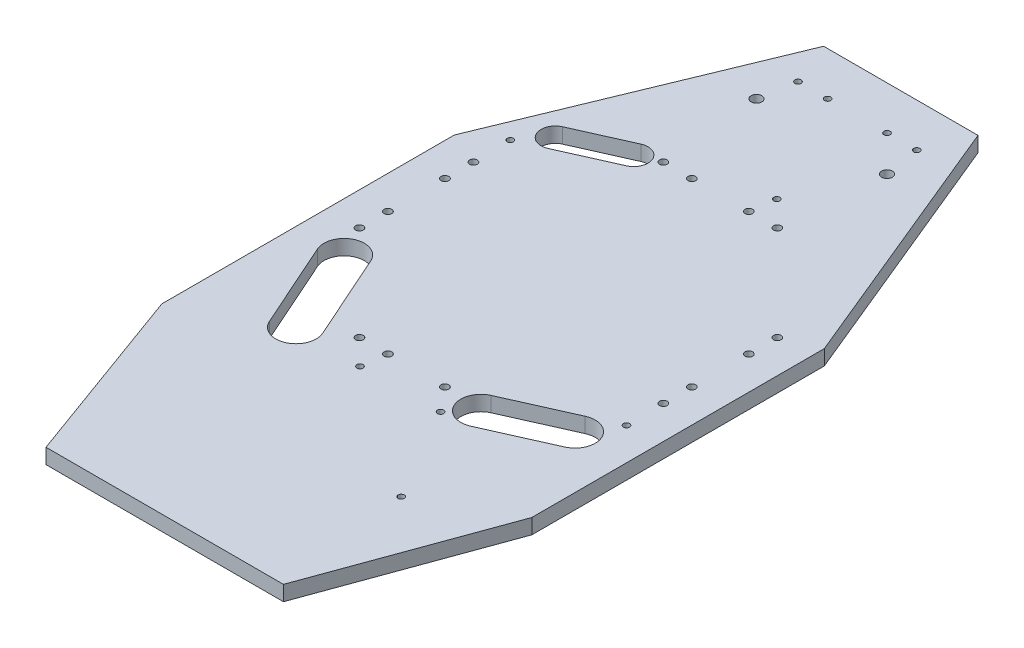
SolidWorks part; units mm, degrees
material "Pin"
ref_plane "Plan de face" through (0, 0, 0) normal (0, 0, 1) x (1, 0, 0)
ref_plane "Plan de dessus" through (0, 0, 0) normal (0, 1, 0) x (1, 0, 0)
ref_plane "Plan de droite" through (0, 0, 0) normal (1, 0, 0) x (0, 0, -1)
sketch "Esquisse3" plane through (0, 0, 0) normal (0, 1, 0) x (1, 0, 0)
  line L0 (-32.5, 140) -> (32.5, 140)
  line L1 (-77.9068, 29.8751) -> (-77.9068, -93.3266)
  line L2 (-77.9068, -93.3266) -> (-50, -170)
  line L3 (-50, -170) -> (50, -170)
  line L5 (77.9068, -93.3266) -> (77.9068, 29.8751)
  line L6 (50, -170) -> (77.9068, -93.3266)
  line L7 (-32.5, 140) -> (-77.9068, 29.8751)
  line L8 (32.5, 140) -> (77.9068, 29.8751)
  point P2 (0, 140)
  point P7 (0, -170)
  dimension "D1" = 170
  dimension "D2" = 140
  dimension "D3" = 65
  dimension "D4" = 70
  dimension "D5" = 100
sketch "TB_boltPattern" plane through (0, 0, 0) normal (0, 1, 0) x (1, 0, 0)
  line L0 (0, 143.3581) -> (0, -141.7362) construction
  line L1 (-23, 57.7) -> (-13, 57.7) construction
  line L2 (-23, 57.7) -> (-23, 43.7) construction
  line L3 (-23, 43.7) -> (-13, 43.7) construction
  line L4 (-13, 57.7) -> (-13, 43.7) construction
  line L5 (-57.7, 23) -> (-43.7, 23) construction
  line L6 (-57.7, 23) -> (-57.7, 13) construction
  line L7 (-57.7, 13) -> (-43.7, 13) construction
  line L8 (-43.7, 23) -> (-43.7, 13) construction
  line L9 (-204.4729, 0) -> (279.6048, 0) construction
  circle A0 centre (-24, 64) radius 1.6 construction
  circle A1 centre (-12, 64) radius 1.6 construction
  circle A2 centre (-64, 24) radius 1.6 construction
  circle A3 centre (-64, 12) radius 1.6 construction
  point P8 (-18, 57.7)
  dimension "D5" = 3.2
  dimension "D10" = 6.3
  dimension "D1" = 12
  dimension "D2" = 12
  dimension "D3" = 40
  dimension "D4" = 40
  dimension "D6" = 14
  dimension "D7" = 10
  dimension "D8" = 1
  dimension "D9" = 6.3
  dimension "D11" = 1
  dimension "D12" = 12
  dimension "D13" = 12
sketch "HB_Footprint" plane through (0, 0, 0) normal (0, 1, 0) x (1, 0, 0)
  line L0 (13.3793, 74.3875) -> (64.2603, -39.7884) construction
  line L1 (64.2603, -39.7884) -> (-13.3793, -74.3875) construction
  line L2 (13.3793, 74.3875) -> (-64.2603, 39.7884) construction
  line L3 (-64.2603, 39.7884) -> (-13.3793, -74.3875) construction
  line L8 (29.8751, 77.9068) -> (-77.9068, 29.8751) construction
  line L9 (-77.9068, 29.8751) -> (-29.8751, -77.9068) construction
  line L10 (-29.8751, -77.9068) -> (77.9068, -29.8751) construction
  line L11 (29.8751, 77.9068) -> (77.9068, -29.8751) construction
  line L12 (53.891, 24.0158) -> (-53.891, -24.0158) construction
  line L13 (-25.4405, 57.0879) -> (0, 0) construction
  circle A0 centre (13.3793, 74.3875) radius 1.6 construction
  circle A1 centre (64.2603, -39.7884) radius 1.6 construction
  circle A2 centre (-64.2603, 39.7884) radius 1.6 construction
  circle A3 centre (-13.3793, -74.3875) radius 1.6 construction
  point P10 (-53.891, -24.0158)
  point P19 (38.8198, 17.2996)
  dimension "D4" = 3.2
  dimension "D1" = 125
  dimension "D2" = 85
  dimension "D3" = 118
extrude "Plate" add sketch "Esquisse3" against normal blind 6.35
ref_axis "Axe1" through (0, 0, 0) along (0, 1, 0)
hole_wizard "Dégagement M32" positions "Esquisse9" profile "Esquisse10" hole size "M3" standard "Ansi Metric"
sketch "Esquisse9" plane through (0, 0, 0) normal (0, 1, 0) x (1, 0, 0)
  point P0 (-24, 64)
  point P3 (-12, 64)
  point P6 (-64, 24)
  point P9 (-64, 12)
sketch "Esquisse10" plane through (-24, 0, -64) normal (1, 0, 0) x (0, 0, 1)
  line L0 (0, 0) -> (0, 7.3114)
  line L1 (0, 7.3114) -> (1.6, 6.35)
  line L2 (1.6, 6.35) -> (1.6, 0)
  line L5 (1.6, 0) -> (0, 0)
  line L10 (0, 7.3114) -> (-1.6, 6.35) construction
  line L11 (0, -6.35) -> (0, 107.95) construction
  dimension "Diamètre du perçage" = 3.2
  dimension "Profondeur du perçage" = 6.35
  dimension "Angle de pointe" = 118
pattern_circular "Répétition circulaire2" count 4 over 360 about axis through (0, 0, 0) along (0, 1, 0) of "Dégagement M32"
hole_wizard "Dégagement M33" positions "Esquisse11" profile "Esquisse12" hole size "M3" standard "Ansi Metric"
sketch "Esquisse11" plane through (0, 0, 0) normal (0, 1, 0) x (1, 0, 0)
  point P0 (13.3793, 74.3875)
  point P3 (-64.2603, 39.7884)
  point P6 (-13.3793, -74.3875)
  point P9 (64.2603, -39.7884)
sketch "Esquisse12" plane through (13.3793, 0, -74.3875) normal (1, 0, 0) x (0, 0, 1)
  line L0 (0, 0) -> (0, 7.1311)
  line L1 (0, 7.1311) -> (1.3, 6.35)
  line L2 (1.3, 6.35) -> (1.3, 0)
  line L5 (1.3, 0) -> (0, 0)
  line L10 (0, 7.1311) -> (-1.3, 6.35) construction
  line L11 (0, -6.35) -> (0, 107.95) construction
  dimension "Diamètre du perçage" = 2.6
  dimension "Profondeur du perçage" = 6.35
  dimension "Angle de pointe" = 118
sketch "RegFootprint" plane through (0, 0, 0) normal (0, 1, 0) x (1, 0, 0)
  line L0 (27.48, 106.69) -> (-27.48, 106.69) construction
  line L2 (0, 79) -> (0, 106.69) construction
  line L3 (0, 200143.3581) -> (0, -200141.7362) construction
  line L4 (32.355, 79) -> (-32.355, 79) construction
  line L5 (32.355, 79) -> (32.355, 138.35) construction
  line L6 (32.355, 138.35) -> (-32.355, 138.35) construction
  line L7 (-32.355, 79) -> (-32.355, 138.35) construction
  line L8 (32.5, 140) -> (-32.5, 140) construction
  circle A0 centre (27.48, 106.69) radius 4.7701 construction
  circle A1 centre (-27.48, 106.69) radius 4.7701 construction
  circle A2 centre (12, 64) radius 1.6 construction
  point P4 (-31.5067, 170.618)
  point P8 (-85.837, 208.5527)
  point P9 (49.7222, 117.5736)
  point P13 (0, 0)
  point P14 (0, 79)
  point P17 (32.4415, 165.5032)
  point P20 (32.7199, 142.7624)
  dimension "D1" = 54.96
  dimension "D2" = 27.69
  dimension "D3" = 64.71
  dimension "D4" = 59.35
  dimension "D5" = 15
hole_wizard "Dégagement M51" positions "Esquisse16" profile "Esquisse17" hole size "M5" standard "Ansi Metric"
sketch "Esquisse16" plane through (0, 0, 0) normal (0, 1, 0) x (1, 0, 0)
  point P0 (27.48, 106.69)
  point P3 (-27.48, 106.69)
sketch "Esquisse17" plane through (27.48, 0, -106.69) normal (1, 0, 0) x (0, 0, 1)
  line L0 (0, 0) -> (0, 7.714)
  line L1 (0, 7.714) -> (2.27, 6.35)
  line L2 (2.27, 6.35) -> (2.27, 0)
  line L5 (2.27, 0) -> (0, 0)
  line L10 (0, 7.714) -> (-2.27, 6.35) construction
  line L11 (0, -6.35) -> (0, 107.95) construction
  dimension "Diamètre du perçage" = 4.54
  dimension "Profondeur du perçage" = 6.35
  dimension "Angle de pointe" = 118
sketch "puckFootprint" plane through (0, 0, 0) normal (0, 1, 0) x (1, 0, 0)
  line L0 (42.8335, -113.2396) -> (20.1785, -74) construction
  line L1 (-29.8568, -164.7163) -> (-60.7468, -111.2133) construction
  line L2 (31.506, -93.6198) -> (-45.3018, -137.9648) construction
  line L4 (31.506, -93.6198) -> (44.4964, -86.1198) construction
  line L7 (0, 200143.3581) -> (0, -200141.7362) construction
  circle A1 centre (20.1785, -74) radius 1.5 construction
  circle A2 centre (42.8335, -113.2396) radius 1.5 construction
  circle A3 centre (-60.7468, -111.2133) radius 1.5 construction
  circle A4 centre (-29.8568, -164.7163) radius 1.5 construction
  circle A5 centre (24, -64) radius 1.6 construction
  point P8 (0, -111.8098)
  point P11 (-25.6517, -126.6198)
  point P12 (0, 0)
  point P16 (74.8755, -425.5387)
  point P17 (70.056, -355.2747)
  point P19 (0, 0)
  point P20 (-37.2769, -223.5735)
  point P21 (-33.1557, -252.1317)
  point P22 (0, 0)
  point P23 (75.9498, -415.6514)
  point P26 (0, 0)
  point P27 (0, -102.3699)
  dimension "D4" = 3
  dimension "D9" = 10
  dimension "D1" = 36.38
  dimension "D2" = 45.31
  dimension "D3" = 52.31
  dimension "D5" = 61.78
  dimension "D6" = 15
  dimension "D7" = 60
  dimension "D8" = 81
hole_wizard "BoltPatternPuck" positions "Esquisse3D1" profile "Esquisse18" hole size "M3" standard "Ansi Metric"
sketch3d "Esquisse3D1"
  point P2 (20.1785, 0, 74)
  point P5 (42.8335, 0, 113.2396)
sketch "Esquisse18" plane through (20.1785, 0, 74) normal (1, 0, 0) x (0, 0, 1)
  line L0 (0, 0) -> (0, 7.1311)
  line L1 (0, 7.1311) -> (1.3, 6.35)
  line L2 (1.3, 6.35) -> (1.3, 0)
  line L5 (1.3, 0) -> (0, 0)
  line L10 (0, 7.1311) -> (-1.3, 6.35) construction
  line L11 (0, -6.35) -> (0, 107.95) construction
  dimension "Diamètre du perçage" = 2.6
  dimension "Profondeur du perçage" = 6.35
  dimension "Angle de pointe" = 118
sketch "Esquisse19" plane through (0, 0, 0) normal (0, 1, 0) x (1, 0, 0)
  line L0 (28.2989, -65.1199) -> (55.7011, -52.9085) construction
  line L1 (24.839, -57.356) -> (52.2412, -45.1445)
  line L2 (31.7588, -72.8839) -> (59.161, -60.6724)
  line L3 (64.2603, -39.7884) -> (-13.3793, -74.3875) construction
  line L4 (-297.1395, 500.9461) -> (-280.8576, 464.4098) construction
  line L5 (-289.3756, 504.406) -> (-273.0936, 467.8697)
  line L6 (-304.9035, 497.4862) -> (-288.6216, 460.9499)
  line L7 (-77.9068, 29.8751) -> (-29.8751, -77.9068) construction
  line L8 (42.8335, -113.2396) -> (20.1785, -74) construction
  line L9 (-57.3809, -37.0665) -> (-41.099, -73.6028) construction
  line L10 (-49.617, -33.6066) -> (-33.3351, -70.1429)
  line L11 (-65.1449, -40.5264) -> (-48.863, -77.0627)
  line L13 (-29.8751, -77.9068) -> (77.9068, -29.8751) construction
  line L14 (-55.6779, 50.1818) -> (-32.8427, 60.358) construction
  line L15 (-58.1202, 55.6623) -> (-35.285, 65.8385)
  line L16 (-53.2356, 44.7014) -> (-30.4004, 54.8776)
  line L17 (13.3793, 74.3875) -> (-64.2603, 39.7884) construction
  arc A0 (24.839, -57.356) -> (31.7588, -72.8839) centre (28.2989, -65.1199) ccw
  arc A1 (59.161, -60.6724) -> (52.2412, -45.1445) centre (55.7011, -52.9085) ccw
  circle A2 centre (12, -64) radius 1.6 construction
  arc A3 (-289.3756, 504.406) -> (-304.9035, 497.4862) centre (-297.1395, 500.9461) ccw
  arc A4 (-288.6216, 460.9499) -> (-273.0936, 467.8697) centre (-280.8576, 464.4098) ccw
  arc A5 (-49.617, -33.6066) -> (-65.1449, -40.5264) centre (-57.3809, -37.0665) ccw
  arc A6 (-48.863, -77.0627) -> (-33.3351, -70.1429) centre (-41.099, -73.6028) ccw
  arc A7 (-58.1202, 55.6623) -> (-53.2356, 44.7014) centre (-55.6779, 50.1818) ccw
  arc A8 (-30.4004, 54.8776) -> (-35.285, 65.8385) centre (-32.8427, 60.358) ccw
  point P2 (42, -59.0142)
  point P13 (-49.24, -55.3347)
  point P15 (-288.9986, 482.678)
  point P33 (-44.2603, 55.2699)
  point P40 (-79.1564, 41.656)
  point P41 (-54.7424, 54.3417)
  point P42 (-60.7262, 48.3578)
  point P43 (0, 0)
  dimension "D5" = 8.5
  dimension "D8" = 6
  dimension "D1" = 17
  dimension "D2" = 30
  dimension "D3" = 30
  dimension "D4" = 40
  dimension "D6" = 40
  dimension "D7" = 25
  dimension "D9" = 20
sketch "WeigthAddOnFootprint" plane through (0, 0, 0) normal (0, 1, 0) x (1, 0, 0)
  line L0 (-25, 121.69) -> (25, 121.69) construction
  line L1 (-12.5, 121.69) -> (12.5, 121.69) construction
  line L2 (0, 200143.3581) -> (0, -200141.7362) construction
  line L4 (27.48, 106.69) -> (-27.48, 106.69) construction
  point P2 (-12.5, 121.69)
  point P3 (12.5, 121.69)
  point P4 (-239.8099, 84.871)
  point P7 (0, 121.69)
  point P8 (0, 121.69)
  dimension "D1" = 50
  dimension "D2" = 25
  dimension "D3" = 15
hole_wizard "Dégagement M35" positions "Esquisse3D2" profile "Esquisse22" hole size "M3" standard "Ansi Metric" end condition up to next
sketch3d "Esquisse3D2"
  point P0 (-25, 0, -121.69)
  point P3 (-12.5, 0, -121.69)
  point P6 (12.5, 0, -121.69)
  point P9 (25, 0, -121.69)
sketch "Esquisse22" plane through (-25, 0, -121.69) normal (1, 0, 0) x (0, 0, 1)
  line L0 (0, 0) -> (0, 6.35)
  line L1 (0, 6.35) -> (1.3, 6.35)
  line L2 (1.3, 6.35) -> (1.3, 0)
  line L5 (1.3, 0) -> (0, 0)
  line L11 (0, -6.35) -> (0, 107.95) construction
  dimension "Diamètre du perçage jusqu'au prochain" = 2.6
  dimension "Profondeur du perçage jusqu'au prochain" = 6.35
extrude "HarnessClearance" cut sketch "Esquisse19" against normal up to surface (6.35 mm away) up to face at (-25, -6.35, -120.39)
